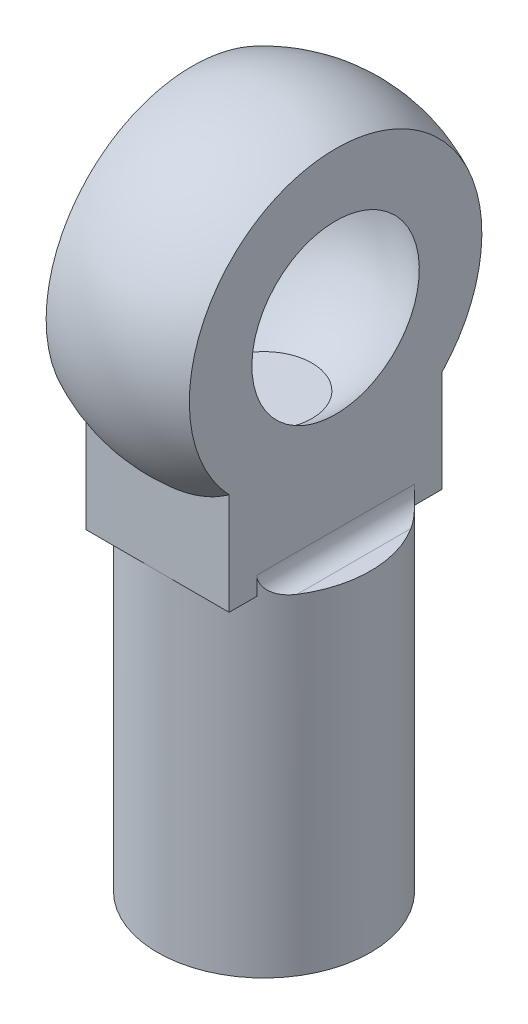
SolidWorks part; units mm, degrees
ref_plane "前视基准面" through (0, 0, 0) normal (0, 0, 1) x (1, 0, 0)
ref_plane "上视基准面" through (0, 0, 0) normal (0, 1, 0) x (1, 0, 0)
ref_plane "右视基准面" through (0, 0, 0) normal (1, 0, 0) x (0, 0, -1)
sketch "草图1" plane through (0, 0, 0) normal (0, 0, 1) x (1, 0, 0)
  line L0 (0, 4.435) -> (0, -4.435)
  arc A0 (0, -4.435) -> (0, 4.435) centre (0, 0) ccw
  dimension "D1" = 8.87
revolve "旋转1" add sketch "草图1" angle 360 about L0
sketch "草图2" plane through (0, 0, 0) normal (0, 0, 1) x (1, 0, 0)
  line L1 (-1.95, 4.9315) -> (-1.95, -5.5616)
  line L2 (1.95, 4.9315) -> (1.95, -5.5616)
  line L3 (-1.95, 4.9315) -> (-9.4819, 1.1065)
  line L4 (-9.4819, 1.1065) -> (-1.95, -5.5616)
  line L5 (1.95, -5.5616) -> (8.4414, -0.1099)
  line L6 (8.4414, -0.1099) -> (1.95, 4.9315)
  point P4 (0, 0)
extrude "切除-拉伸1" cut sketch "草图2" against normal mid plane 20
ref_plane "基准面1" through (0, 0, 0) normal (-1, 0, 0) x (0, 0, 1)
sketch "草图3" plane through (0, 0, 0) normal (-1, 0, 0) x (0, 0, 1)
  line L0 (0, 3) -> (0, -3)
  arc A0 (0, -3) -> (0, 3) centre (0, 0) ccw
  dimension "D1" = 6
revolve "切除-旋转1" cut sketch "草图3" angle 360 about L0
sketch "草图4" plane through (0, 0, 0) normal (-1, 0, 0) x (0, 0, 1)
  line L1 (-2.9, -2.7) -> (2.9, -2.7)
  line L2 (-2.9, -2.7) -> (-2.9, -5.5)
  line L3 (-2.9, -5.5) -> (2.9, -5.5)
  line L4 (2.9, -2.7) -> (2.9, -5.5)
  dimension "D1" = 5.8
  dimension "D2" = 2.9
  dimension "D3" = 5.5
extrude "凸台-拉伸2" add sketch "草图4" along normal up to surface (1.95 mm away)
sketch "草图5" plane through (0, 0, 0) normal (1, 0, 0) x (0, 0, -1)
  line L3 (2.9, -5.5) -> (2.9, -3.3555)
  line L4 (-2.9, -3.3555) -> (-2.9, -5.5)
  line L5 (-2.9, -5.5) -> (2.9, -5.5)
  line L6 (2.9, -5.5) -> (2.9, -3.3555)
  line L7 (-2.9, -3.3555) -> (-2.9, -5.5)
  line L8 (-2.9, -5.5) -> (2.9, -5.5)
  arc A1 (-2.9, -3.3555) -> (2.9, -3.3555) centre (0, 0) ccw
  arc A2 (-2.9, -3.3555) -> (2.9, -3.3555) centre (0, 0) ccw
  dimension "D1" = 0
sketch "草图6" plane through (1.95, 0, 0) normal (1, 0, 0) x (0, 0, -1)
  line L0 (2.9, -5.5) -> (-2.9, -5.5) construction
  line L1 (-2.9, -2.7) -> (-2.9, -5.5) construction
  line L2 (2.9, -2.7) -> (2.9, -5.5) construction
  line L3 (2.9, -2.7) -> (-2.9, -2.7) construction
  line L4 (2.9, -5.5) -> (-2.9, -5.5)
  line L5 (-2.9, -2.7) -> (-2.9, -5.5)
  line L6 (2.9, -2.7) -> (2.9, -5.5)
  line L7 (2.9, -2.7) -> (-2.9, -2.7)
extrude "凸台-拉伸4" add sketch "草图6" against normal up to surface (1.95 mm away) up to face at (0, -4.6976, 0)
sketch "草图7" plane through (0, -5.5, 0) normal (0, -1, 0) x (1, 0, 0)
  circle A0 centre (0, 0) radius 2.9
  dimension "D1" = 5.8
extrude "凸台-拉伸5" add sketch "草图7" along normal blind 9
fillet "圆角1" radius 0.5 2 edges at (-1.95, -5.5, 0) (1.95, -5.5, 0)
sketch "草图8" plane through (0, -14.5, 0) normal (0, -1, 0) x (1, 0, 0)
  circle A0 centre (0, 0) radius 1.5
  dimension "D1" = 3
extrude "切除-拉伸2" cut sketch "草图8" against normal blind 8
